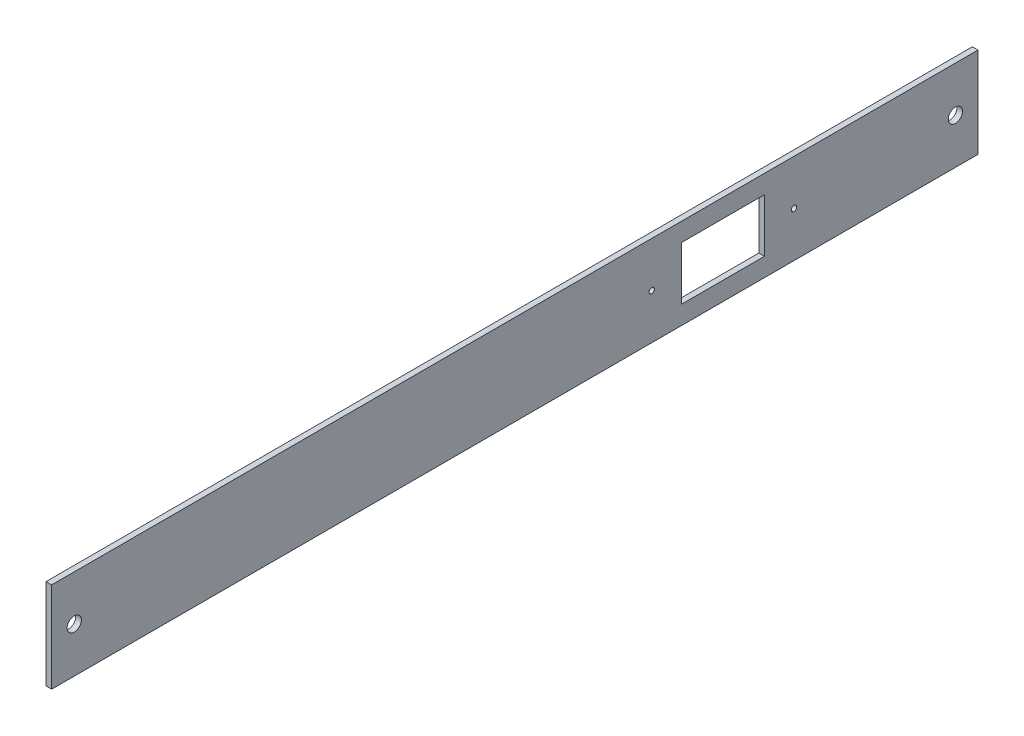
SolidWorks part; units mm, degrees
ref_plane "Front Plane" through (0, 0, 0) normal (0, 0, 1) x (1, 0, 0)
ref_plane "Top Plane" through (0, 0, 0) normal (0, 1, 0) x (1, 0, 0)
ref_plane "Right Plane" through (0, 0, 0) normal (1, 0, 0) x (0, 0, -1)
sketch "Sketch1" plane through (0, 0, 0) normal (1, 0, 0) x (0, 0, -1)
  line L1 (0, 0) -> (520.7, 0)
  line L2 (0, 0) -> (0, 50.8)
  line L3 (0, 50.8) -> (520.7, 50.8)
  line L4 (520.7, 0) -> (520.7, 50.8)
  circle A0 centre (12.7, 25.4) radius 4
  circle A1 centre (508, 25.4) radius 4
  dimension "D3" = 8
  dimension "D1" = 50.8
  dimension "D2" = 520.7
  dimension "D4" = 25.4
  dimension "D5" = 12.7
  dimension "D6" = 12.7
  dimension "D7" = 508
extrude "Boss-Extrude2" add sketch "Sketch1" along normal blind 3.175
sketch "ACOutletSketch2" plane through (3.175, 0, 0) normal (1, 0, 0) x (0, 0, -1)
  line L0 (520.7, 50.8) -> (0, 50.8) construction
  line L1 (353.9, 40.4) -> (400.7, 40.4)
  line L2 (353.9, 40.4) -> (353.9, 10.4)
  line L3 (353.9, 10.4) -> (400.7, 10.4)
  line L4 (400.7, 40.4) -> (400.7, 10.4)
  line L5 (520.7, 0) -> (520.7, 50.8) construction
  line L6 (0, 50.8) -> (0, 0) construction
  dimension "D1" = 46.8
  dimension "D2" = 30
  dimension "D3" = 10.4
  dimension "D4" = 120
  dimension "D5" = 353.9
  dimension "D6" = 400.7
extrude "ACOutletCut-Extrude1" cut sketch "ACOutletSketch2" against normal through all
sketch "PowerCoverMountingHolesSketch2" plane through (3.175, 0, 0) normal (1, 0, 0) x (0, 0, -1)
  line L0 (400.7, 10.4) -> (400.7, 40.4) construction
  line L1 (353.9, 40.4) -> (353.9, 10.4) construction
  line L2 (0, 50.8) -> (0, 0) construction
  circle A0 centre (337.3, 25.4) radius 1.5
  circle A1 centre (417.3, 25.4) radius 1.5
  point P8 (353.9, 25.4)
  point P12 (0, 25.4)
  dimension "D1" = 80
  dimension "D2" = 16.6
  dimension "D3" = 16.6
  dimension "D5" = 337.3
  dimension "D6" = 417.3
extrude "PowerCoverMountingHolesCut-Extrude1" cut sketch "PowerCoverMountingHolesSketch2" against normal through all
equation "\"RailThickness\"= .125in'Spec"
equation "\"VSWidth\"= 1.25in'Spec"
equation "\"LowerRailHeight\"= 2.0in"
equation "\"StepperHolePadSize\"= \"StepperHoleDiameter\""
equation "\"D1@Sketch1\"=\"LowerRailHeight\""
equation "\"D2@Sketch1\"= \"FrontOrBackRailLength\""
equation "\"FrameFastenerHoleDiameter\"= 8mm"
equation "\"D3@Sketch1\"=\"FrameFastenerHoleDiameter\""
equation "\"D4@Sketch1\"=\"LowerRailHeight\"/2"
equation "\"D5@Sketch1\"=\"FrameFastenerHoleOffsetFromEdge\""
equation "\"D6@Sketch1\"=\"FrameFastenerHoleOffsetFromEdge\""
equation "\"D1@Boss-Extrude2\"=\"RailThickness\""
equation "\"FrontOrBackRailLength\"= 20.5in"
equation "\"FrameFastenerHoleOffsetFromEdge\"= \"VSWidth\" / 2 - \"GapBetweenVerticalSupportsAndRails\" / 2"
equation "\"GapBetweenVerticalSupportsAndRails\"= \"RailThickness\" * 2"
equation "\"ACPowerOutletHeight\"= 30mm"
equation "\"D2@ACOutletSketch2\"=\"ACPowerOutletHeight\""
equation "\"ACPowerOutletWidth\"= 46.8mm"
equation "\"D1@ACOutletSketch2\"=\"ACPowerOutletWidth\""
equation "\"D3@ACOutletSketch2\"=(\"LowerRailHeight\"-\"ACPowerOutletHeight\")/2"
equation "\"AngleBracketSmallHoleDiameter\"= 4mm"
equation "\"AngleBracketSlotDistanceBetweenHoles\"= 30mm"
equation "\"AngleBracketSlotDistanceFromTop\"= 13mm"
equation "\"AngleBracketSlotDistanceFromCorner\"= \"AngleBracketSlotDistanceFromBack\" - \"GapBetweenVerticalSupportsAndRails\" / 2'Equals 61.825"
equation "\"AngleBracketSlotDistanceFromBack\"= 65mm"
equation "\"D2@PowerCoverMountingHolesSketch2\"=( \"PowerSwitchCoverWidthBetweenMountingHoles\" - \"ACPowerOutletWidth\" )  / 2"
equation "\"PowerSwitchCoverWidth\"= 70mm"
equation "\"PowerSwitchCoverMountingTabWidth\"= 10mm"
equation "\"PowerSwitchCoverWidthBetweenMountingHoles\"= \"PowerSwitchCoverWidth\" + \"PowerSwitchCoverMountingTabWidth\""
equation "\"D1@PowerCoverMountingHolesSketch2\"=\"PowerSwitchCoverWidthBetweenMountingHoles\""
